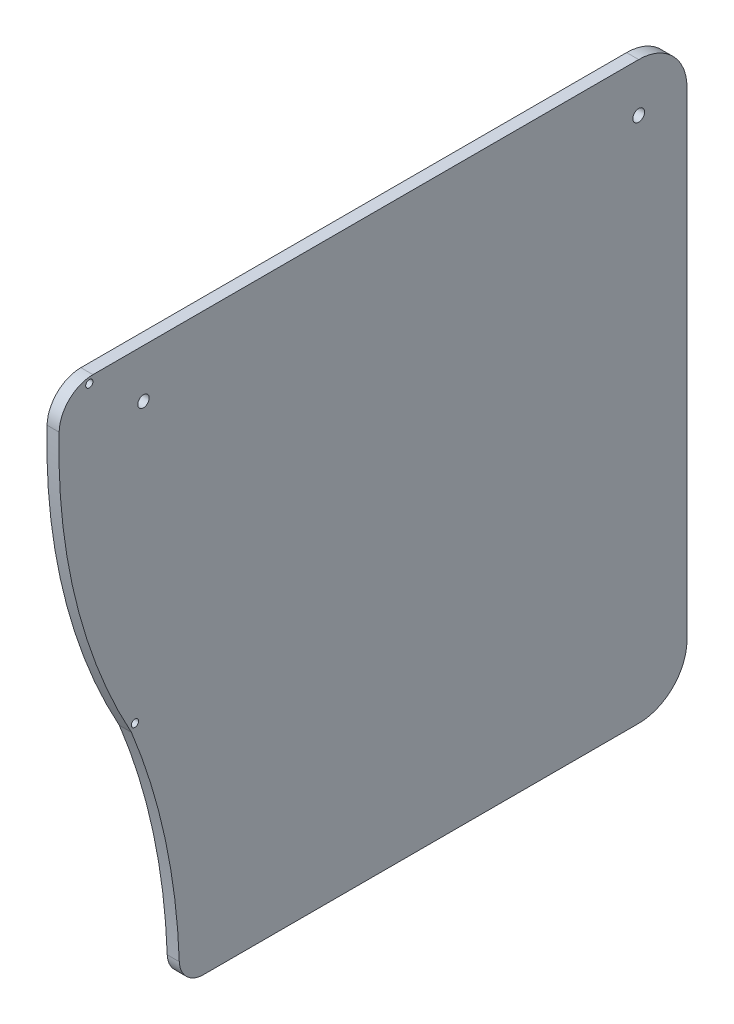
SolidWorks part; units mm, degrees
ref_plane "Front Plane" through (0, 0, 0) normal (0, 0, 1) x (1, 0, 0)
ref_plane "Top Plane" through (0, 0, 0) normal (0, 1, 0) x (1, 0, 0)
ref_plane "Right Plane" through (0, 0, 0) normal (1, 0, 0) x (0, 0, -1)
sketch "Sketch1" plane through (0, 0, 0) normal (1, 0, 0) x (0, 0, -1)
  line L1 (-82.55, 75.565) -> (82.55, 75.565)
  line L2 (-82.55, 75.565) -> (-82.55, -75.565)
  line L3 (-82.55, -75.565) -> (82.55, -75.565)
  line L4 (82.55, 75.565) -> (82.55, -75.565)
  line L9 (69.85, 75.565) -> (69.85, -75.565) construction
  circle A0 centre (69.85, 62.865) radius 1.55
  arc A1 (69.85, -75.565) -> (82.55, -62.865) centre (69.85, -62.865) ccw
  arc A2 (82.55, 62.865) -> (69.85, 75.565) centre (69.85, 62.865) ccw
  point P4 (-82.55, 0)
  point P6 (0, 75.565)
  dimension "D6" = 3.1
  dimension "D1" = 165.1
  dimension "D3" = 151.13
  dimension "D4" = 12.7
  dimension "D5" = 12.7
  dimension "D7" = 12.7
extrude "Boss-Extrude1" add sketch "Sketch1" along normal blind 3.175 contours L9 L1 L2 L3 A0 | L1 L9 A1 L4 region at (0, -0.0191, 0.243)
sketch "Sketch2" plane through (3.175, 0, 0) normal (1, 0, 0) x (0, 0, -1)
  line L0 (-63.5, -75.565) -> (-50.8, -75.565)
  line L2 (-82.55, 62.865) -> (-82.55, -75.565)
  line L3 (-82.55, -75.565) -> (-63.5, -75.565)
  line L5 (-82.55, 75.565) -> (-82.0199, 75.565)
  line L6 (-82.55, 75.565) -> (69.85, 75.565) construction
  line L7 (-82.55, 75.565) -> (-82.55, 62.865)
  line L8 (-63.5, -10.9153) -> (-63.5, -75.565)
  line L9 (82.55, 62.865) -> (82.55, -62.865) construction
  line L11 (-50.8, 75.565) -> (-50.8, -75.565) construction
  line L12 (-82.55, -75.565) -> (69.85, -75.565) construction
  arc A1 (-82.0199, 75.565) -> (-63.5, -10.9153) centre (69.85, 62.865) ccw
  arc A4 (-50.8, -75.565) -> (-63.5, -10.9153) centre (-221.7004, -75.565) ccw
  line M6 (69.85, 75.565) -> (-82.55, 75.565)
  line M7 (-82.55, 75.565) -> (-82.55, -75.565)
  line M8 (-82.55, -75.565) -> (69.85, -75.565)
  dimension "D1" = 146.05
  dimension "D2" = 133.35
extrude "Cut-Extrude1" cut sketch "Sketch2" against normal through all contours A1 M7 M8 | A1 M6 M7 | A4 L8 M8 region at (3.175, -51.1966, 58.4035) region at (3.175, 72.3911, 82.391) region at (3.175, -29.5833, 74.0728)
fillet "Fillet1" radius 8.89 1 edges at (1.5875, 75.565, 82.0199)
sketch "Sketch3" plane through (3.175, 0, 0) normal (1, 0, 0) x (0, 0, -1)
  line L0 (-73.6094, 75.565) -> (69.85, 75.565) construction
  circle A0 centre (-60.325, 62.865) radius 1.5
  dimension "D1" = 3
  dimension "D2" = 9.525
  dimension "D3" = 12.7
extrude "Cut-Extrude2" cut sketch "Sketch3" against normal through all
sketch "Sketch4" plane through (3.175, 0, 0) normal (1, 0, 0) x (0, 0, -1)
  line L0 (-73.6094, 72.39) -> (-73.6094, 75.565)
  line L1 (-60.7219, -9.3782) -> (-63.5, -10.9153)
  line L2 (-74.5619, 73.9775) -> (-73.6094, 73.9775) construction
  line L3 (-62.1109, -10.1468) -> (-62.5721, -9.3134) construction
  arc A0 (-82.4963, 66.911) -> (-63.5, -10.9153) centre (69.85, 62.865) ccw construction
  arc A1 (-73.6094, 75.565) -> (-82.4963, 66.911) centre (-73.6094, 66.675) ccw construction
  arc A2 (-82.4963, 66.911) -> (-63.5, -10.9153) centre (69.85, 62.865) ccw
  arc A3 (-73.6094, 75.565) -> (-82.4963, 66.911) centre (-73.6094, 66.675) ccw
  arc A4 (-73.6094, 72.39) -> (-79.3224, 66.8267) centre (-73.6094, 66.675) ccw
  arc A5 (-79.3224, 66.8267) -> (-60.7219, -9.3782) centre (69.85, 62.865) ccw
  circle A6 centre (-74.5619, 73.9775) radius 0.9525
  circle A7 centre (-62.5721, -9.3134) radius 0.9525
  dimension "D2" = 1.905
  dimension "D1" = 3.175
extrude "Cut-Extrude3" cut sketch "Sketch4" against normal through all contours A6 | A7 region at (3.175, 73.9775, 74.5619) region at (3.175, -9.3134, 62.5721)
fillet "Fillet2" radius 6.35 1 edges at (1.5875, -75.565, 50.8)
equation "\"bottomThickness\"= .25in"
equation "\"wallThickness\"= .125in"
equation "\"D1@Boss-Extrude1\"=\"wallThickness\""
